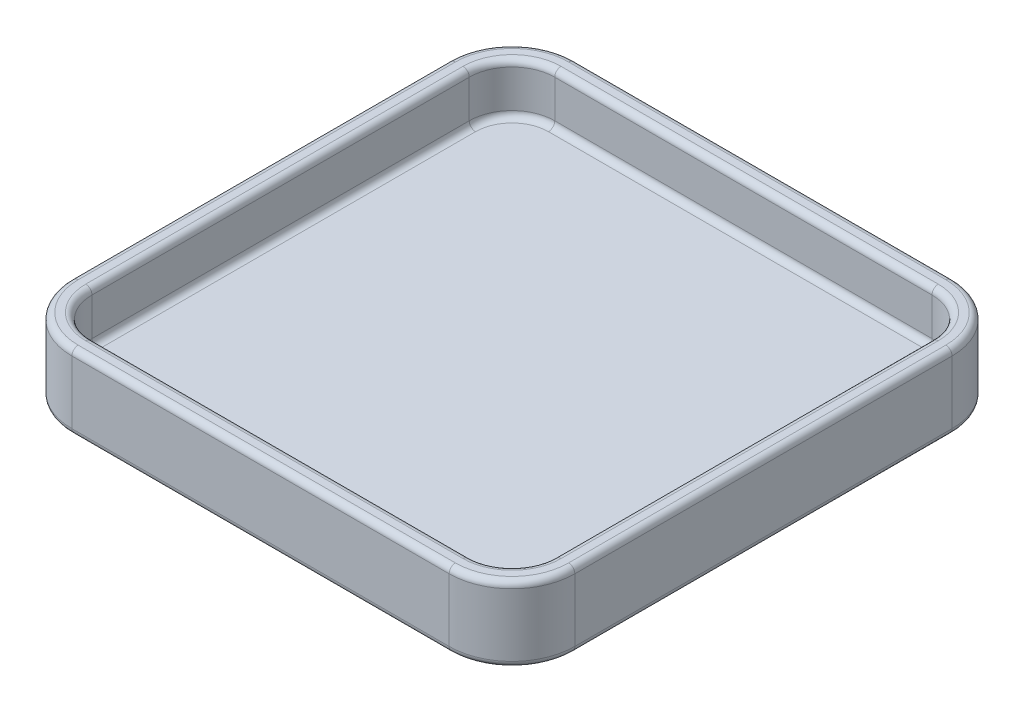
SolidWorks part; units mm, degrees
material "ABS"
ref_plane "Front Plane" through (0, 0, 0) normal (0, 0, 1) x (1, 0, 0)
ref_plane "Top Plane" through (0, 0, 0) normal (0, 1, 0) x (1, 0, 0)
ref_plane "Right Plane" through (0, 0, 0) normal (1, 0, 0) x (0, 0, -1)
sketch "Sketch1" plane through (0, 0, 0) normal (0, 1, 0) x (1, 0, 0)
  line L1 (-15, 20) -> (15, 20)
  line L2 (-20, 15) -> (-20, -15)
  line L3 (-15, -20) -> (15, -20)
  line L4 (20, 15) -> (20, -15)
  line L5 (-20, 20) -> (20, -20) construction
  line L6 (-20, -20) -> (20, 20) construction
  arc A0 (-20, -15) -> (-15, -20) centre (-15, -15) ccw
  arc A1 (-15, 20) -> (-20, 15) centre (-15, 15) ccw
  arc A2 (15, 20) -> (20, 15) centre (15, 15) cw
  arc A3 (15, -20) -> (20, -15) centre (15, -15) ccw
  point P0 (0, 0)
  dimension "D2" = 5
  dimension "D1" = 40
extrude "Boss-Extrude1" add sketch "Sketch1" along normal blind 2
extrude "Extrude-Thin1" add sketch "Sketch1<2>" along normal blind 4 from surface thin starting at face at (0, 2, 0) thin type one direction reverse wall 1.6
sketch "Sketch1<2>" plane through (0, 0, 0) normal (0, 1, 0) x (1, 0, 0) same geometry as "Sketch1"
fillet "Fillet1" radius 0.5 32 edges at (18.5355, 6, -18.5355) (0, 6, -20) (-18.5355, 6, -18.5355) (-20, 6, 0) (-18.5355, 6, 18.5355) (0, 6, 20) (18.5355, 6, 18.5355) (18.5355, 0, 18.5355) (0, 0, 20) (-18.5355, 0, 18.5355) (-20, 0, 0) (-18.5355, 0, -18.5355) (0, 0, -20) (18.5355, 0, -18.5355) (20, 6, 0) (20, 0, 0) (-17.4042, 6, -17.4042) (-18.4, 6, 0) (-17.4042, 6, 17.4042) (0, 6, 18.4) (17.4042, 6, 17.4042) (18.4, 6, 0) (17.4042, 6, -17.4042) (-17.4042, 2, -17.4042) (-18.4, 2, 0) (-17.4042, 2, 17.4042) (0, 2, 18.4) (17.4042, 2, 17.4042) (18.4, 2, 0) (17.4042, 2, -17.4042) (0, 6, -18.4) (0, 2, -18.4)
